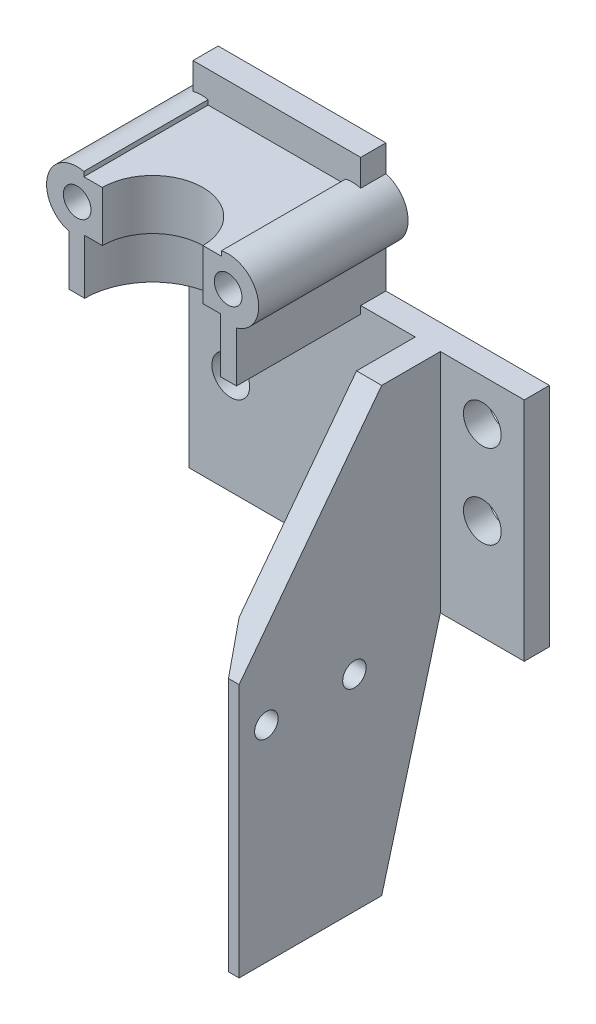
SolidWorks part; units mm, degrees
ref_plane "前视基准面" through (0, 0, 0) normal (0, 0, 1) x (1, 0, 0)
ref_plane "上视基准面" through (0, 0, 0) normal (0, 1, 0) x (1, 0, 0)
ref_plane "右视基准面" through (0, 0, 0) normal (1, 0, 0) x (0, 0, -1)
other "Configuration Table"
sketch "Sketch2" plane through (0, 0, 0) normal (0, 0, 1) x (1, 0, 0)
  line L1 (-20, 13.5) -> (20, 13.5)
  line L2 (-20, 13.5) -> (-20, -13.5)
  line L3 (-20, -13.5) -> (20, -13.5)
  line L4 (20, 13.5) -> (20, -13.5)
  circle A0 centre (-15, 8.5) radius 2.25
  circle A1 centre (15, 8.5) radius 2.25
  circle A2 centre (15, -1.5) radius 2.25
  circle A3 centre (-15, -1.5) radius 2.25
  dimension "D1" = 2
  dimension "D2" = 2
extrude "Boss-Extrude1" add sketch "Sketch2" along normal blind 3
sketch "Sketch3" plane through (0, 13.5, 0) normal (0, 1, 0) x (1, 0, 0)
  line L0 (20, -3) -> (-20, -3) construction
  line L1 (-19.5, 0) -> (0.5, 0)
  line L2 (-19.5, 0) -> (-19.5, -3)
  line L3 (-19.5, -3) -> (0.5, -3)
  line L4 (0.5, 0) -> (0.5, -3)
  arc A0 (-9.5, -25.8158) -> (-9.5, -9.8158) centre (-9.5, -17.8158) ccw construction
  dimension "D1" = 10
  dimension "D2" = 10
extrude "Boss-Extrude2" add sketch "Sketch3" along normal up to surface (15.3 mm away)
sketch "Sketch4" plane through (0, 19.1, 0) normal (0, 1, 0) x (1, 0, 0)
  line L0 (-19.5, -3) -> (-19.5, -17.8158)
  line L1 (-19.5, -17.8158) -> (-15.5, -17.8158)
  line L2 (-3.5, -17.8158) -> (0.5, -17.8158)
  line L3 (0.5, -17.8158) -> (0.5, -3)
  line L4 (0.5, -3) -> (-19.5, -3)
  arc A0 (-9.5, -23.8158) -> (-9.5, -11.8158) centre (-9.5, -17.8158) ccw construction
  arc A1 (-3.5, -17.8158) -> (-9.5, -11.8158) centre (-9.5, -17.8158) ccw
  arc A6 (-9.5, -11.8158) -> (-9.5, -23.8158) centre (-9.5, -17.8158) ccw construction
  arc A7 (-9.5, -11.8158) -> (-15.5, -17.8158) centre (-9.5, -17.8158) ccw
extrude "Boss-Extrude3" add sketch "Sketch4" along normal up to surface (6 mm away)
sketch "Sketch5" plane through (0, 19.1, 0) normal (0, -1, 0) x (1, 0, 0)
  line L5 (-19.5, 3) -> (0.5, 3)
  line L6 (0.5, 3) -> (0.5, 17.8158)
  line L7 (0.5, 17.8158) -> (-3.5, 17.8158)
  line L8 (-15.5, 17.8158) -> (-19.5, 17.8158)
  line L9 (-19.5, 17.8158) -> (-19.5, 3)
  line L10 (-19.5, 3) -> (0.5, 3)
  line L11 (0.5, 3) -> (0.5, 17.8158)
  line L12 (0.5, 17.8158) -> (-1.4, 17.8158)
  line L13 (-17.6, 17.8158) -> (-19.5, 17.8158)
  line L14 (-19.5, 17.8158) -> (-19.5, 3)
  arc A1 (-15.5, 17.8158) -> (-3.5, 17.8158) centre (-9.5, 17.8158) ccw
  arc A6 (-17.6, 17.8158) -> (-9.5, 9.7158) centre (-9.5, 17.8158) ccw
  arc A7 (-9.5, 9.7158) -> (-1.4, 17.8158) centre (-9.5, 17.8158) ccw
  dimension "D1" = 0
extrude "Boss-Extrude4" add sketch "Sketch5" along normal offset from surface (6.5 mm away) 0.5
sketch "Sketch6" plane through (0, 0, 3) normal (0, 0, 1) x (1, 0, 0)
  line L0 (20, 13.5) -> (0.5, 13.5) construction
  line L1 (10, -39.2) -> (7, -39.2)
  line L2 (10, -39.2) -> (10, 13.5)
  line L3 (10, 13.5) -> (7, 13.5)
  line L4 (7, -39.2) -> (7, 13.5)
  dimension "D1" = 3
extrude "Boss-Extrude5" add sketch "Sketch6" along normal up to surface (24 mm away)
sketch "Sketch7" plane through (10, 0, 0) normal (1, 0, 0) x (0, 0, -1)
  circle A0 centre (-23.75, -14.7) radius 1.4
  circle A1 centre (-13.25, -14.7) radius 1.4
extrude "Cut-Extrude1" cut sketch "Sketch7" against normal blind 5
sketch "Sketch8" plane through (10, 0, 0) normal (1, 0, 0) x (0, 0, -1)
  line L0 (-3, -13.5) -> (-10, -39.2)
  line L1 (-27, -39.2) -> (-3, -39.2) construction
  line L2 (-10, -39.2) -> (-3, -39.2)
  line L3 (-3, -39.2) -> (-3, -13.5)
  line L4 (-10, 13.5) -> (-27, -8.9)
  line L5 (-27, 13.5) -> (-3, 13.5) construction
  line L6 (-27, -39.2) -> (-27, 13.5) construction
  line L7 (-28.9658, -8.9) -> (-6.6658, -8.9) construction
  line L8 (-27, -8.9) -> (-27, 13.5)
  line L9 (-27, 13.5) -> (-10, 13.5)
extrude "Cut-Extrude2" cut sketch "Sketch8" against normal blind 5
sketch "Sketch9" plane through (0, 0, 17.8158) normal (0, 0, 1) x (1, 0, 0)
  line L0 (-15.5, 25.1) -> (-19.5, 25.1) construction
  line L1 (-15.5, 25.1) -> (-15.5, 19.1) construction
  circle A0 centre (-18.5, 22.1) radius 1.65
  circle A1 centre (-0.5, 22.1) radius 1.65
  dimension "D1" = 3.3
  dimension "D2" = 3
  dimension "D3" = 3
  dimension "D4" = 2
extrude "Cut-Extrude3" cut sketch "Sketch9" against normal blind 20
sketch "Sketch10" plane through (0, 0, 17.8158) normal (0, 0, 1) x (1, 0, 0)
  line L0 (-19.5, 25.1) -> (-19.5, 23.4124)
  line L1 (-19.5, 28.8) -> (-19.5, 25.1) construction
  line L2 (-19.5, 20.7876) -> (-19.5, 12.6) construction
  line L3 (0.5, 25.1) -> (0.5, 23.4124)
  line L4 (0.5, 20.7876) -> (0.5, 12.6) construction
  line L5 (-19.5, 20.7876) -> (-19.5, 18.5897)
  line L6 (0.5, 20.7876) -> (0.5, 18.5897)
  line L7 (-19.5, 25.1) -> (-17.7, 25.1)
  line L10 (-17.5, 28.8) -> (-17.5, 25.1) construction
  line L11 (0.5, 25.1) -> (-1.3, 25.1)
  line L14 (-1.5, 25.1) -> (-1.5, 28.8) construction
  line L15 (-17.7, 25.1) -> (-17.7, 25.6612)
  line L17 (-1.3, 25.1) -> (-1.3, 25.6612)
  arc A0 (-19.5, 25.6103) -> (-19.5, 18.5897) centre (-18.5, 22.1) ccw
  arc A1 (0.5, 18.5897) -> (0.5, 25.6103) centre (-0.5, 22.1) ccw
  arc A2 (-19.5, 20.7876) -> (-19.5, 23.4124) centre (-18.5, 22.1) ccw construction
  arc A3 (0.5, 23.4124) -> (0.5, 20.7876) centre (-0.5, 22.1) ccw construction
  arc A4 (-19.5, 23.4124) -> (-19.5, 20.7876) centre (-18.5, 22.1) ccw
  arc A5 (0.5, 20.7876) -> (0.5, 23.4124) centre (-0.5, 22.1) ccw
  arc A6 (-17.7, 25.6612) -> (-19.5, 18.5897) centre (-18.5, 22.1) ccw
  arc A7 (0.5, 18.5897) -> (-1.3, 25.6612) centre (-0.5, 22.1) ccw
  line M1 (-19.5, 25.1) -> (-19.5, 23.4124)
  line M3 (-19.5, 20.7876) -> (-19.5, 12.6)
  line M8 (-15.5, 25.1) -> (-19.5, 25.1)
  dimension "D1" = 2
  dimension "D2" = 2
  dimension "D3" = 0.2
  dimension "D4" = 0.2
extrude "Boss-Extrude6" add sketch "Sketch10" against normal up to surface (17.8158 mm away) contours L15 A6 A0 A4 M3 M1 M8 | A1 A7 L17 L11 L3 A5 L6 region at (-20.5125, 22.367, 17.8158) region at (1.5125, 22.367, 17.8158) up to face at (-6.3333, 14.4167, 0)
chamfer "Chamfer1" distance 3 angle 30 1 edges at (7, -24.05, 27) first distance on face at (7, -14.7, 22.35)
